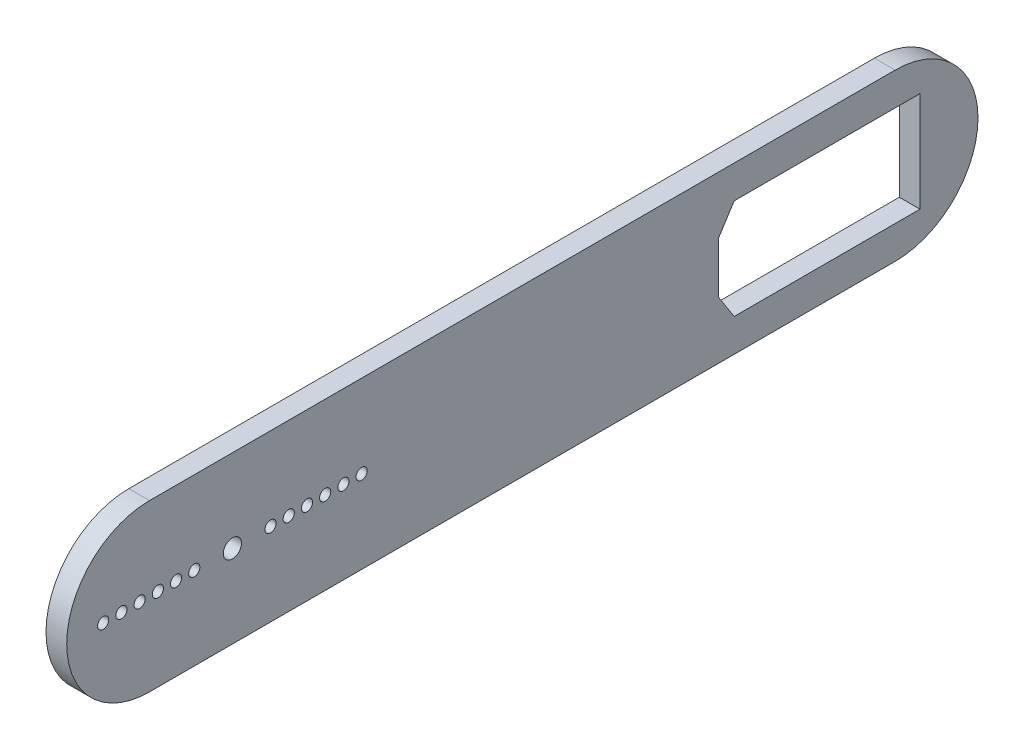
SolidWorks part; units mm, degrees
ref_plane "Front Plane" through (0, 0, 0) normal (0, 0, 1) x (1, 0, 0)
ref_plane "Top Plane" through (0, 0, 0) normal (0, 1, 0) x (1, 0, 0)
ref_plane "Right Plane" through (0, 0, 0) normal (1, 0, 0) x (0, 0, -1)
sketch "Sketch1" plane through (0, 0, 0) normal (1, 0, 0) x (0, 0, -1)
  line L1 (-55, -10) -> (55, -10)
  line L2 (-55, -10) -> (-55, 10)
  line L3 (-55, 10) -> (55, 10)
  line L4 (55, -10) -> (55, 10)
  line L5 (-55, -10) -> (55, 10) construction
  line L6 (-55, 10) -> (55, -10) construction
  point P0 (0, 0)
  dimension "D1" = 20
  dimension "D2" = 110
extrude "Boss-Extrude1" add sketch "Sketch1" along normal mid plane 2.5
sketch "Sketch2" plane through (1.25, 0, 0) normal (1, 0, 0) x (0, 0, -1)
  line L0 (-35, 10) -> (-35, -10) construction
  line L1 (55, 10) -> (-55, 10) construction
  line L2 (-55, -10) -> (55, -10) construction
  line L3 (-55, 0) -> (-35, 0) construction
  line L4 (-55, 10) -> (-55, -10) construction
  circle A0 centre (-35, 0) radius 1.1
  dimension "D2" = 2.2
  dimension "D1" = 20
extrude "Cut-Extrude1" cut sketch "Sketch2" against normal through all both and the other way through all
sketch "Sketch3" plane through (1.25, 0, 0) normal (1, 0, 0) x (0, 0, -1)
  line L0 (-55, 0) -> (55, 0) construction
  line L1 (-55, 10) -> (-55, -10) construction
  line L2 (55, -10) -> (55, 10) construction
  circle A0 centre (-50.6, 0) radius 0.675
  circle A1 centre (-48.4, 0) radius 0.675
  circle A2 centre (-46.2, 0) radius 0.675
  circle A3 centre (-44, 0) radius 0.675
  circle A4 centre (-41.8, 0) radius 0.675
  circle A5 centre (-39.6, 0) radius 0.675
  circle A6 centre (-30.4, 0) radius 0.675
  circle A7 centre (-28.2, 0) radius 0.675
  circle A8 centre (-26, 0) radius 0.675
  circle A9 centre (-23.8, 0) radius 0.675
  circle A10 centre (-21.6, 0) radius 0.675
  circle A11 centre (-19.4, 0) radius 0.675
  dimension "D1" = 6
  dimension "D2" = 6
extrude "Cut-Extrude2" cut sketch "Sketch3" against normal through all both
sketch "Sketch4" plane through (1.25, 0, 0) normal (1, 0, 0) x (0, 0, -1)
  line L0 (25.5697, 0) -> (23.7012, 0) construction
  line L1 (25.5697, -6.0415) -> (48, -6.0415)
  line L2 (25.5697, -6.0415) -> (25.5697, 6.0415) construction
  line L3 (25.5697, 6.0415) -> (48, 6.0415)
  line L4 (48, -6.0415) -> (48, 6.0415)
  line L5 (25.5697, -6.0415) -> (48, 6.0415) construction
  line L6 (25.5697, 6.0415) -> (48, -6.0415) construction
  line L7 (23.7012, -3.1261) -> (23.7012, 3.1261)
  line L8 (23.7012, 3.1261) -> (25.5697, 6.0415)
  line L9 (23.7012, -3.1261) -> (25.5697, -6.0415)
  line L10 (55, -10) -> (55, 10) construction
  line L14 (0, 0) -> (50000, 0) construction
  point P4 (36.7848, 0)
  point P10 (23.7012, 0)
  dimension "D1" = 7
  dimension "D2" = 12.0831
  dimension "D3" = 22.4303
  dimension "D5" = 32.656
  dimension "D6" = 1.8685
extrude "Cut-Extrude3" cut sketch "Sketch4" against normal through all both and the other way through all
fillet "Fillet2" 2 edges at (0, 10, -55) (0, -10, -55) type full round first side face at (0, 10, 0) second side face at (0, -10, 0) middle face at (0, 0, -55)
fillet "Fillet3" 2 edges at (0, 10, 55) (0, -10, 55) type full round first side face at (0, 10, 5) second side face at (0, -10, 5) middle face at (0, 0, 55)
